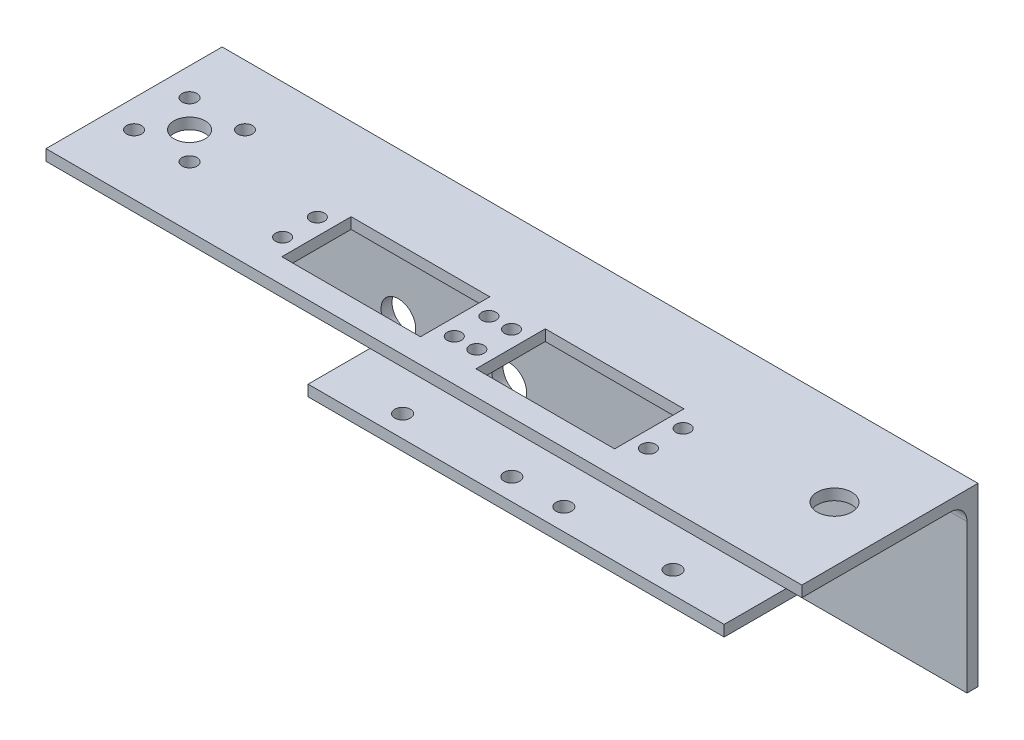
SolidWorks part; units mm, degrees
material "6061 Alloy"
ref_plane "Front Plane" through (0, 0, 0) normal (0, 0, 1) x (1, 0, 0)
ref_plane "Top Plane" through (0, 0, 0) normal (0, 1, 0) x (1, 0, 0)
ref_plane "Right Plane" through (0, 0, 0) normal (1, 0, 0) x (0, 0, -1)
sketch "Sketch1" plane through (0, 0, 0) normal (1, 0, 0) x (0, 0, -1)
  line L0 (0, 0) -> (50.8, 0)
  line L1 (50.8, 0) -> (50.8, -3.175)
  line L2 (50.8, -3.175) -> (3.175, -3.175)
  line L3 (3.175, -3.175) -> (3.175, -47.625)
  line L5 (0, -50.8) -> (0, 0)
  line L6 (0, -50.8) -> (50.8, -50.8)
  line L7 (50.8, -50.8) -> (50.8, -47.625)
  line L8 (50.8, -47.625) -> (3.175, -47.625)
  line L9 (3.175, -47.625) -> (0, -47.625) construction
  dimension "D1" = 50.8
extrude "Base Angle Profile" add sketch "Sketch1" along normal mid plane 218
sketch "Sketch2" plane through (0, 0, 0) normal (0, 1, 0) x (1, 0, 0)
  line L1 (-48, 43.8) -> (-8, 43.8)
  line L2 (-48, 43.8) -> (-48, 23.8)
  line L3 (-48, 23.8) -> (-8, 23.8)
  line L4 (-8, 43.8) -> (-8, 23.8)
  line L5 (-48, 43.8) -> (-8, 23.8) construction
  line L6 (-48, 23.8) -> (-8, 43.8) construction
  line L7 (8, 43.8) -> (48, 43.8)
  line L8 (8, 43.8) -> (8, 23.8)
  line L9 (8, 23.8) -> (48, 23.8)
  line L10 (48, 43.8) -> (48, 23.8)
  line L11 (8, 43.8) -> (48, 23.8) construction
  line L12 (8, 23.8) -> (48, 43.8) construction
  line L13 (-52.75, 38.8) -> (-52.75, 28.8) construction
  line L14 (-3.25, 28.8) -> (-3.25, 38.8) construction
  line L15 (3.25, 28.8) -> (3.25, 38.8) construction
  line L16 (52.75, 28.8) -> (52.75, 38.8) construction
  line L17 (109, 50.8) -> (-109, 50.8) construction
  line L18 (-3.25, 33.8) -> (3.25, 33.8) construction
  circle A0 centre (-52.75, 38.8) radius 2.05
  circle A1 centre (-52.75, 28.8) radius 2.05
  circle A2 centre (-3.25, 38.8) radius 2.05
  circle A3 centre (-3.25, 28.8) radius 2.05
  circle A4 centre (3.25, 28.8) radius 2.05
  circle A5 centre (3.25, 38.8) radius 2.05
  circle A6 centre (52.75, 38.8) radius 2.05
  circle A7 centre (52.75, 28.8) radius 2.05
  point P4 (-28, 33.8)
  point P9 (28, 33.8)
  point P10 (0, 33.8)
  point P28 (-52.75, 33.8)
  dimension "D5" = 4.1
  dimension "D1" = 20
  dimension "D2" = 40
  dimension "D3" = 16
  dimension "D6" = 4.75
  dimension "D7" = 10
  dimension "D8" = 4.75
  dimension "D9" = 4.75
  dimension "D10" = 4.75
  dimension "D11" = 7
extrude "Servo Mount Pattern" cut sketch "Sketch2" against normal up to surface (3.175 mm away) up to face at (0, -3.175, -26.9875)
fillet "Internal Fillet" radius 4.7752 1 edges at (0, -3.175, -3.175)
sketch "Sketch3" plane through (0, 0, 0) normal (0, 1, 0) x (1, 0, 0)
  line L0 (93, 25.4) -> (109, 25.4) construction
  line L1 (101, 33.4) -> (85, 33.4) construction
  line L2 (101, 33.4) -> (101, 17.4) construction
  line L3 (101, 17.4) -> (85, 17.4) construction
  line L4 (85, 33.4) -> (85, 17.4) construction
  line L5 (101, 33.4) -> (85, 17.4) construction
  line L6 (101, 17.4) -> (85, 33.4) construction
  line L7 (109, 50.8) -> (109, 0) construction
  line L10 (48, 23.8) -> (48, 43.8) construction
  circle A0 centre (93, 25.4) radius 4.5
  circle A1 centre (101, 33.4) radius 2.15
  circle A2 centre (85, 33.4) radius 2.15
  circle A3 centre (85, 17.4) radius 2.15
  circle A4 centre (101, 17.4) radius 2.15
  circle A5 centre (93, 25.4) radius 16 construction
  point P7 (93, 25.4)
  dimension "D1" = 4.3
  dimension "D2" = 9
  dimension "D6" = 32
  dimension "D3" = 16
  dimension "D4" = 16
  dimension "D5" = 45
extrude "Lead Screw Nut Pattern" cut sketch "Sketch3" against normal up to surface (3.175 mm away) up to face at (52.75, -3.175, -36.75)
sketch "Sketch4" plane through (0, 0, 0) normal (0, 1, 0) x (1, 0, 0)
  line L1 (93, 25.4) -> (-93, 25.4) construction
  circle A0 centre (-93, 25.4) radius 5
  circle A1 centre (-52.75, 28.8) radius 2.05 construction
  dimension "D1" = 10
  dimension "D2" = 40.25
extrude "Cut-Extrude3" cut sketch "Sketch4" against normal up to surface (3.175 mm away) up to face at (101, -3.175, -15.25)
sketch "Sketch5" plane through (0, -50.8, 0) normal (0, -1, 0) x (1, 0, 0)
  line L0 (-109, -3.175) -> (-60, -3.175)
  line L1 (-109, 0) -> (-109, -50.8) construction
  line L2 (-60, -3.175) -> (-60, -24.205)
  line L3 (-60, -24.205) -> (60, -24.205)
  line L4 (60, -24.205) -> (60, -3.175)
  line L5 (60, -3.175) -> (109, -3.175)
  line L6 (109, 0) -> (109, -50.8) construction
  line L7 (109, -3.175) -> (109, -50.8)
  line L8 (109, -50.8) -> (-109, -50.8)
  line L9 (-109, -50.8) -> (-109, -3.175)
  line L10 (109, 0) -> (-109, 0) construction
  point P16 (0, -24.205)
  dimension "D1" = 3.175
  dimension "D2" = 21.03
  dimension "D3" = 120
extrude "Channel Bottom Cut" cut sketch "Sketch5" against normal blind 10
sketch "Sketch7" plane through (0, 0, -3.175) normal (0, 0, -1) x (-1, 0, 0)
  line L0 (-60, -47.625) -> (60, -47.625) construction
  line L1 (-60, -47.625) -> (-60, -50.8) construction
  line L2 (60, -47.625) -> (60, -50.8) construction
  circle A0 centre (-55, -39.295) radius 5
  circle A1 centre (-23, -39.295) radius 5
  circle A2 centre (23, -39.295) radius 5
  circle A3 centre (55, -39.295) radius 5
  dimension "D4" = 10
  dimension "D1" = 32
  dimension "D2" = 32
  dimension "D3" = 8.33
  dimension "D5" = 5
  dimension "D6" = 5
extrude "Cut-Extrude5" cut sketch "Sketch7" against normal through all
sketch "Sketch8" plane through (0, -50.8, 0) normal (0, -1, 0) x (-1, 0, 0)
  line L0 (60, 24.205) -> (60, 3.175) construction
  line L1 (-60, 3.175) -> (-60, 24.205) construction
  line L2 (-60, 24.205) -> (60, 24.205) construction
  circle A0 centre (39, 17.955) radius 2.25
  circle A1 centre (7.5, 17.955) radius 2.25
  circle A2 centre (-7.5, 17.955) radius 2.25
  circle A3 centre (-39, 17.955) radius 2.25
  dimension "D1" = 4.5
  dimension "D2" = 21
  dimension "D3" = 15
  dimension "D4" = 7.5
  dimension "D5" = 21
  dimension "D6" = 6.25
extrude "Cut-Extrude6" cut sketch "Sketch8" against normal up to surface (3.175 mm away) up to face at (0, -47.625, -13.69)
move or copy body "Body-Move/Copy1" bodies to move or copy 110 copy no rotation origin (0, 0, -25.4) rotation axis (0, 1, 0) rotation angle 180
equation "\"Angle-Width\"= 25.4 * 2"
equation "\"D1@Sketch1\"=\"Angle-Width\""
equation "\"Angle-Thickness\"= 25.4 / 8"
equation "\"D8@Sketch2\"=\"D6@Sketch2\""
equation "\"D9@Sketch2\"=\"D6@Sketch2\""
equation "\"D10@Sketch2\"=\"D6@Sketch2\""
equation "\"D1@Sketch5\"=\"Angle-Thickness\""
equation "\"D4@Sketch8\"=\"D3@Sketch8\"/2"
equation "\"D6@Sketch8\"=12.5/2"
